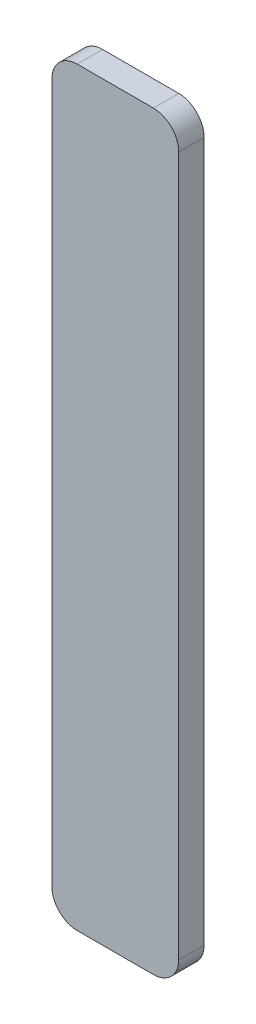
SolidWorks part; units mm, degrees
ref_plane "Front Plane" through (0, 0, 0) normal (0, 0, 1) x (1, 0, 0)
ref_plane "Top Plane" through (0, 0, 0) normal (0, 1, 0) x (1, 0, 0)
ref_plane "Right Plane" through (0, 0, 0) normal (1, 0, 0) x (0, 0, -1)
sketch "Sketch1" plane through (0, 0, 0) normal (0, 0, 1) x (1, 0, 0)
  line L0 (-2.5, 28.58) -> (-2.5, 1)
  line L1 (-1.5, 0) -> (1.5, 0)
  line L2 (-1.5, 29.58) -> (1.5, 29.58)
  line L3 (0, 8.4408) -> (0, 50.6564) construction
  line L4 (2.5, 28.58) -> (2.5, 1)
  arc A0 (-2.5, 1) -> (-1.5, 0) centre (-1.5, 1) ccw
  arc A1 (-2.5, 28.58) -> (-1.5, 29.58) centre (-1.5, 28.58) cw
  arc A2 (2.5, 28.58) -> (1.5, 29.58) centre (1.5, 28.58) ccw
  arc A3 (2.5, 1) -> (1.5, 0) centre (1.5, 1) cw
  point P8 (0, 0)
  point P19 (0, 29.58)
  dimension "D3" = 1
  dimension "D1" = 29.58
  dimension "D2" = 5
extrude "Boss-Extrude1" add sketch "Sketch1" along normal blind 1
equation "\"PCBWidth\" = 5"
equation "\"BearingBaseDistance\"= 12"
equation "\"BearingOD\"= 32"
equation "\"BearingID\" = 25"
equation "\"BearingHeight\"= 4"
equation "\"SeatsOD\"= \"BearingOD\" + 10"
equation "\"WireHarnessHeight\"= 0.05in * 4 + 4.5"
equation "\"OuterWallWidth\"= 5"
equation "\"OverallOD\" = 50"
equation "\"OuterHousingHeight\" = \"WireHarnessHeight\" + \"BearingHeight\"*2 + \"BearingBaseDistance\""
equation "\"RetainingRingThickness\" = 1.30"
equation "\"RetaininRingGrooveDiameter\" = 23.9"
equation "\"ShaftLengthAfterFlange\" = 2*\"BearingHeight\" + \"BearingBaseDistance\" + \"RetainingRingThickness\"*2 'give a retaining ring thickness of extra clearance"
equation "\"RetainingRingGrooveBase\" = \"ShaftLengthAfterFlange\" - \"RetainingRingThickness\"*2"
equation "\"CoverThickness\" = 1"
equation "\"PCBHeight\" = \"OuterHousingHeight\" "
equation "\"CoverClearance\" = 1"
equation "\"FlangHeight\" = \"CoverThickness\" + \"CoverClearance\" + \"WireHarnessHeight\""
equation "\"PCBThickness\" = 1"
equation "\"D1@Boss-Extrude1\"=\"PCBThickness\""
equation "\"D1@Sketch1\"=\"PCBHeight\""
equation "\"D2@Sketch1\"=\"PCBWidth\""
